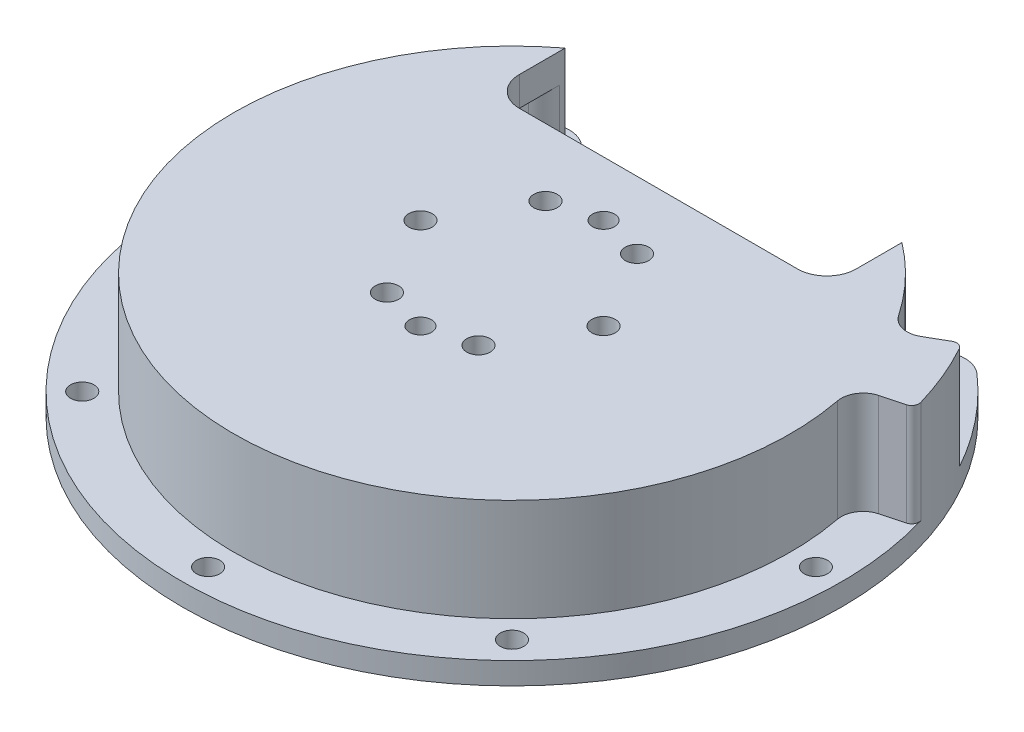
SolidWorks part; units mm, degrees
ref_plane "Спереди" through (0, 0, 0) normal (0, 0, 1) x (1, 0, 0)
ref_plane "Сверху" through (0, 0, 0) normal (0, 1, 0) x (1, 0, 0)
ref_plane "Справа" through (0, 0, 0) normal (1, 0, 0) x (0, 0, -1)
ref_plane "Плоскость4" through (0, 17, 0) normal (0, 1, 0) x (1, 0, 0)
sketch "Эскиз1" plane through (0, 17, 0) normal (0, 1, 0) x (1, 0, 0)
  line L0 (23, 30.8545) -> (23, 27.6948)
  line L1 (-23, 27.6948) -> (-23, 30.8545)
  arc A0 (23, 27.6948) -> (-23, 27.6948) centre (0, 0) ccw
  arc A1 (-23, 30.8545) -> (-29.6341, 33.8647) centre (-27, 30.8545) ccw
  arc A2 (-29.6341, 33.8647) -> (29.6341, 33.8647) centre (0, 0) ccw
  arc A3 (29.6341, 33.8647) -> (23, 30.8545) centre (27, 30.8545) ccw
extrude "Бобышка-Вытянуть1" add sketch "Эскиз1" against normal blind 3
sketch "Эскиз2" plane through (0, 14, 0) normal (0, -1, 0) x (1, 0, 0)
  line L0 (-23, -27.6948) -> (-23, -30.249)
  line L1 (36.7052, -9.8351) -> (43.4667, -11.6469)
  line L2 (38.9711, -22.5) -> (32.909, -19)
  line L3 (23, -30.249) -> (23, -27.6948)
  arc A0 (-23, -30.249) -> (36.7052, -9.8351) centre (0, 0) cw
  arc A1 (43.4667, -11.6469) -> (38.9711, -22.5) centre (0, 0) cw
  arc A2 (32.909, -19) -> (23, -30.249) centre (0, 0) cw
  arc A3 (23, -27.6948) -> (-23, -27.6948) centre (0, 0) cw
extrude "Бобышка-Вытянуть2" add sketch "Эскиз2" along normal blind 14
ref_plane "Плоскость5" through (0, 0, 0) normal (0, -1, 0) x (1, 0, 0)
ref_plane "Плоскость6" through (0, 4, 0) normal (0, 1, 0) x (1, 0, 0)
sketch "Эскиз4" plane through (0, 4, 0) normal (0, 1, 0) x (1, 0, 0)
  line L0 (-23, 27.6948) -> (-23, 20)
  line L1 (-23, 20) -> (23, 20)
  line L2 (23, 20) -> (23, 27.6948)
  arc A0 (23, 27.6948) -> (-23, 27.6948) centre (0, 0) ccw
extrude "Вырез-Вытянуть1" cut sketch "Эскиз4" against normal up to surface up to plane "Плоскость5"
ref_plane "Плоскость7" through (0, 0, 0) normal (0, 0, -1) x (-1, 0, 0)
sketch "Эскиз5" plane through (0, 0, 0) normal (0, 0, -1) x (-1, 0, 0)
  line L0 (-36, 4) -> (0, 4)
  line L1 (0, 4) -> (0, 17)
  line L2 (0, 17) -> (-36, 17)
  line L3 (-36, 17) -> (-36, 4)
  line L4 (0, 4) -> (0, 17) construction
revolve "Вырез-Повернуть1" cut sketch "Эскиз5" angle 360 about L4 reverse direction yes
hole_wizard "Диаметр отверстия Ø3.0 (3)1" positions "Эскиз7" profile "Эскиз6" hole size "Ø3.0" standard "Ansi Metric"
sketch "Эскиз7" plane through (0, 0, 0) normal (0, -1, 0) x (-1, 0, 0)
  point P0 (0, -12.5)
  point P1 (0, 12.5)
sketch "Эскиз6" plane through (0, 0, 12.5) normal (1, 0, 0) x (0, 0, -1)
  line L0 (0, 0) -> (0, 3.9013)
  line L1 (0, 3.9013) -> (1.5, 3)
  line L2 (1.5, 3) -> (1.5, 0)
  line L5 (1.5, 0) -> (0, 0)
  line L10 (0, 3.9013) -> (-1.5, 3) construction
  line L11 (0, -6.35) -> (0, 107.95) construction
  dimension "Диаметр отверстия" = 3
  dimension "Глубина отверстия" = 3
  dimension "Угол заточки сверла" = 118
hole_wizard "Диаметр отверстия Ø3.2 (3.2)1" positions "Эскиз9" profile "Эскиз8" hole size "Ø3.2" standard "Ansi Metric"
sketch "Эскиз9" plane through (0, 17, 0) normal (0, 1, 0) x (1, 0, 0)
  point P0 (29.3449, -29.3449)
  point P1 (0, -41.5)
  point P2 (-29.3449, -29.3449)
  point P3 (-41.5, 0)
  point P4 (-29.3449, 29.3449)
  point P5 (29.3449, 29.3449)
  point P6 (41.5, 0)
sketch "Эскиз8" plane through (29.3449, 17, 29.3449) normal (1, 0, 0) x (0, 0, 1)
  line L0 (0, 0) -> (0, 17)
  line L1 (0, 17) -> (1.6, 17)
  line L2 (1.6, 17) -> (1.6, 0)
  line L5 (1.6, 0) -> (0, 0)
  line L11 (0, -6.35) -> (0, 107.95) construction
  dimension "Диаметр сквозного отверстия" = 3.2
  dimension "Глубина сквозного отверстия" = 17
hole_wizard "Диаметр отверстия Ø3.2 (3.2)2" positions "Эскиз11" profile "Эскиз10" hole size "Ø3.2" standard "Ansi Metric"
sketch "Эскиз11" plane through (0, 4, 0) normal (0, 1, 0) x (1, 0, 0)
  point P0 (-6.25, -10.8253)
  point P1 (6.25, -10.8253)
  point P2 (12.5, 0)
  point P3 (6.25, 10.8253)
  point P4 (-6.25, 10.8253)
  point P5 (-12.5, 0)
sketch "Эскиз10" plane through (-6.25, 4, 10.8253) normal (1, 0, 0) x (0, 0, 1)
  line L0 (0, 0) -> (0, 4)
  line L1 (0, 4) -> (1.6, 4)
  line L2 (1.6, 4) -> (1.6, 0)
  line L5 (1.6, 0) -> (0, 0)
  line L11 (0, -6.35) -> (0, 107.95) construction
  dimension "Диаметр сквозного отверстия" = 3.2
  dimension "Глубина сквозного отверстия" = 4
chamfer "Фаска1" distance 1.55 angle 45 6 edges at (-12.5, 4, 1.6) (6.25, 4, 12.4253) (-6.25, 4, 12.4253) (6.25, 4, -9.2253) (12.5, 4, 1.6) (-6.25, 4, -9.2253)
fillet "Скругление1" radius 1 2 edges at (38.9711, 7, -22.5) (43.4667, 7, -11.6469) tangent propagation no
fillet "Скругление2" radius 3 2 edges at (36.7052, 7, -9.8351) (32.909, 7, -19) tangent propagation no
fillet "Скругление3" radius 4 4 edges at (23, 10.5, -27.6948) (-23, 10.5, -27.6948) (23, 2, -20) (-23, 2, -20) tangent propagation no
mirror "Зеркальное отражение1" about plane through (27, 17, -30.8545) normal (0, 1, 0) of bodies 109
delete or keep bodies "Тело-Удалить/Сохранить 1" type delete bodies bodies 109
